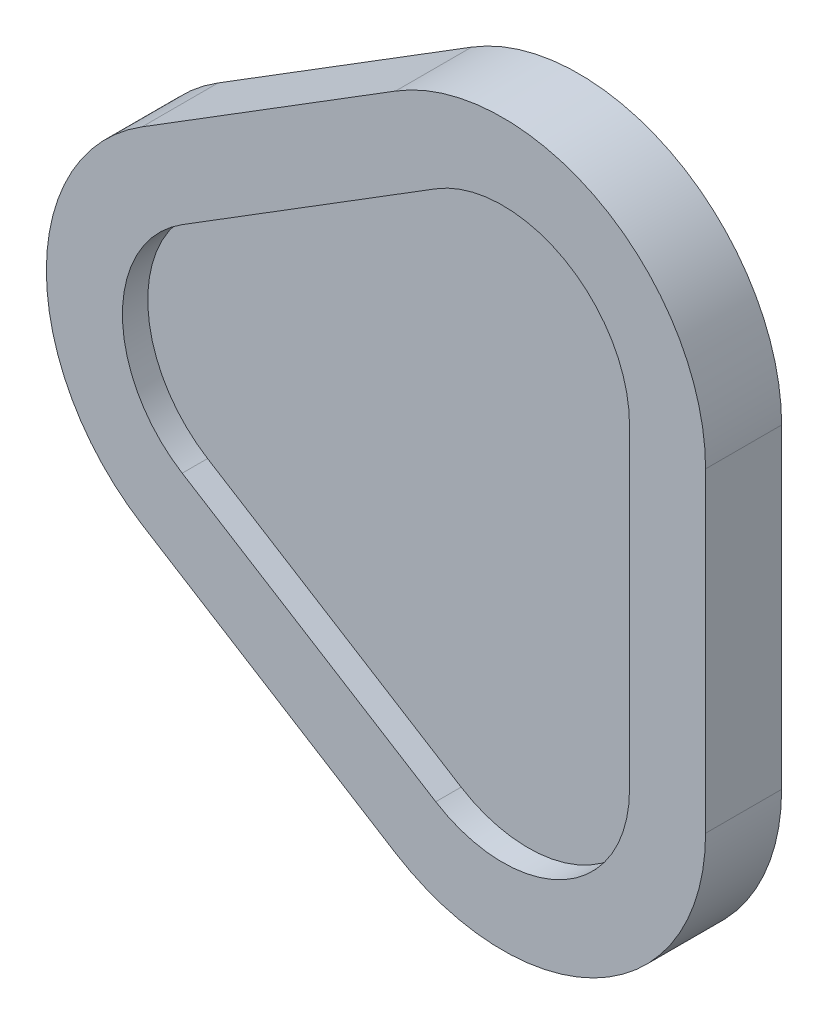
SolidWorks part; units mm, degrees
material "Kaucuk"
ref_plane "Ön Düzlem" through (0, 0, 0) normal (0, 0, 1) x (1, 0, 0)
ref_plane "Üst Düzlem" through (0, 0, 0) normal (0, 1, 0) x (1, 0, 0)
ref_plane "Sağ Düzlem" through (0, 0, 0) normal (1, 0, 0) x (0, 0, -1)
sketch "Çizim1" plane through (0, 0, 0) normal (0, 0, 1) x (1, 0, 0)
  line L0 (-90.9966, -49.6094) -> (-40.9966, -80.7242)
  line L1 (20.1373, -46.7631) -> (20.1373, 15.4665)
  line L2 (-90.9966, 18.3129) -> (-40.9966, 49.4277)
  line L3 (-83.0714, -36.874) -> (-33.0714, -67.9888)
  line L4 (-83.0714, 5.5774) -> (-33.0714, 36.6923)
  line L5 (5.1373, -46.7631) -> (5.1373, 15.4665)
  arc A1 (-83.0714, 5.5774) -> (-83.0714, -36.874) centre (-69.8627, -15.6483) ccw
  arc A2 (5.1373, 15.4665) -> (-33.0714, 36.6923) centre (-19.8627, 15.4665) ccw
  arc A3 (-33.0714, -67.9888) -> (5.1373, -46.7631) centre (-19.8627, -46.7631) ccw
  arc A4 (-40.9966, -80.7242) -> (20.1373, -46.7631) centre (-19.8627, -46.7631) ccw
  arc A5 (20.1373, 15.4665) -> (-40.9966, 49.4277) centre (-19.8627, 15.4665) ccw
  arc A6 (-90.9966, 18.3129) -> (-90.9966, -49.6094) centre (-69.8627, -15.6483) ccw
  dimension "D1" = 50
  dimension "D2" = 50
  dimension "D3" = 50
extrude "Yükseklik-Ekstrüzyon1" add sketch "Çizim1" along normal blind 15 contours L3 A3 L5 A2 L4 A1 | L0 A4 L1 A5 L2 A6
extrude "Boss-Extrude1" add sketch "Çizim1<3>" along normal blind 10 contours L3 A3 L5 A2 L4 A1 region at (-36.2271, -15.6483, 0)
sketch "Çizim1<3>" plane through (0, 0, 0) normal (0, 0, 1) x (1, 0, 0) same geometry as "Çizim1"
